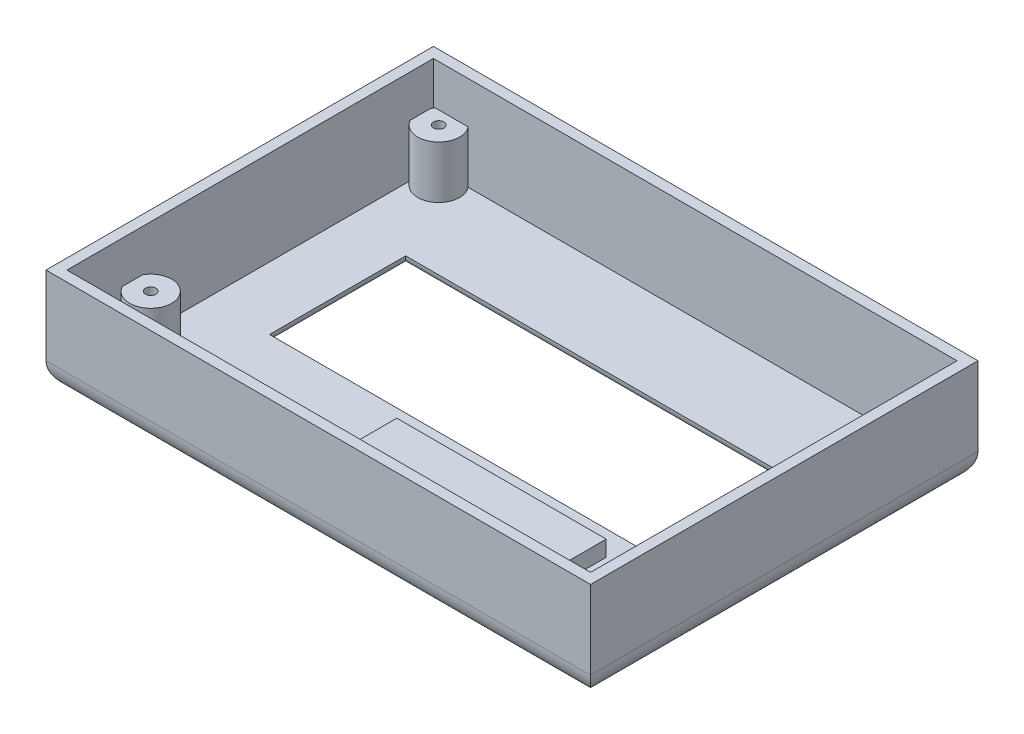
SolidWorks part; units mm, degrees
material "ABS"
ref_plane "Front Plane" through (0, 0, 0) normal (0, 0, 1) x (1, 0, 0)
ref_plane "Top Plane" through (0, 0, 0) normal (0, 1, 0) x (1, 0, 0)
ref_plane "Right Plane" through (0, 0, 0) normal (1, 0, 0) x (0, 0, -1)
sketch "Sketch1" plane through (0, 0, 0) normal (0, 1, 0) x (1, 0, 0)
  line L0 (-83.9438, 0.6974) -> (20.0562, 0.6974)
  line L1 (-69.9438, -18.6026) -> (7.0562, -18.6026)
  line L2 (-69.9438, -18.6026) -> (-69.9438, -44.6026)
  line L3 (-69.9438, -44.6026) -> (7.0562, -44.6026)
  line L4 (7.0562, -18.6026) -> (7.0562, -44.6026)
  line L5 (-81.9438, -1.3026) -> (18.0562, -1.3026)
  line L6 (-81.9438, -1.3026) -> (-81.9438, -71.3026)
  line L7 (-81.9438, -71.3026) -> (18.0562, -71.3026)
  line L8 (18.0562, -1.3026) -> (18.0562, -71.3026)
  line L9 (20.0562, 0.6974) -> (20.0562, -73.3026)
  line L10 (-83.9438, -73.3026) -> (20.0562, -73.3026)
  line L11 (-83.9438, 0.6974) -> (-83.9438, -73.3026)
  circle A0 centre (-26.9438, -61.3026) radius 5.5
  circle A1 centre (-1.9438, -61.3026) radius 5.5
  dimension "D3" = 25
  dimension "D1" = 12
  dimension "D2" = 17.3
  dimension "D4" = 20
  dimension "D5" = 10
  dimension "D7" = 26
  dimension "D8" = 77
  dimension "D6" = 2
extrude "Boss-Extrude2" add sketch "Sketch1" along normal blind 20 contours L6 L7 L8 L5 | L9 L10 L11 L0
extrude "Boss-Extrude3" add sketch "Sketch1<3>" along normal blind 2 contours L8 L5 L6 L7 A1 A0 L1 L4 L3 L2 region at (-31.9438, 0, 2.5233)
sketch "Sketch1<3>" plane through (0, 0, 0) normal (0, 1, 0) x (1, 0, 0) same geometry as "Sketch1"
fillet "Fillet1" radius 5 4 edges at (20.0562, 0, 36.3026) (-31.9438, 0, 73.3026) (-83.9438, 0, 36.3026) (-31.9438, 0, -0.6974)
fillet "Fillet2" radius 2 4 edges at (-69.9438, 0, 31.6026) (-31.4438, 0, 44.6026) (7.0562, 0, 31.6026) (-31.4438, 0, 18.6026)
sketch "Sketch3" plane through (0, 2, 0) normal (0, 1, 0) x (1, 0, 0)
  line L0 (-81.9438, -1.3026) -> (-81.9438, -71.3026) construction
  line L1 (-81.9438, -1.3026) -> (18.0562, -1.3026) construction
  circle A0 centre (-78.4438, -3.8026) radius 4
  circle A1 centre (14.5562, -3.8026) radius 4
  circle A2 centre (-78.4438, -58.8026) radius 4
  circle A3 centre (14.5562, -58.8026) radius 4
  circle A4 centre (-78.4438, -3.8026) radius 1
  circle A5 centre (14.5562, -3.8026) radius 1
  circle A6 centre (14.5562, -58.8026) radius 1
  circle A7 centre (-78.4438, -58.8026) radius 1
  dimension "D1" = 93
  dimension "D3" = 2.5
  dimension "D2" = 3.5
  dimension "D4" = 55
extrude "Boss-Extrude4" add sketch "Sketch3" along normal blind 10
sketch "Sketch4" plane through (0, 0, 71.3026) normal (0, 0, -1) x (-1, 0, 0)
  line L0 (-18.0562, 20) -> (-18.0562, 2) construction
  line L1 (33.9438, 9) -> (-6.0562, 9)
  line L2 (33.9438, 9) -> (33.9438, 12)
  line L3 (33.9438, 12) -> (-6.0562, 12)
  line L4 (-6.0562, 9) -> (-6.0562, 12)
  line L5 (81.9438, 2) -> (-18.0562, 2) construction
  dimension "D1" = 3
  dimension "D2" = 40
  dimension "D3" = 12
  dimension "D4" = 7
extrude "Boss-Extrude5" add sketch "Sketch4" along normal blind 15
